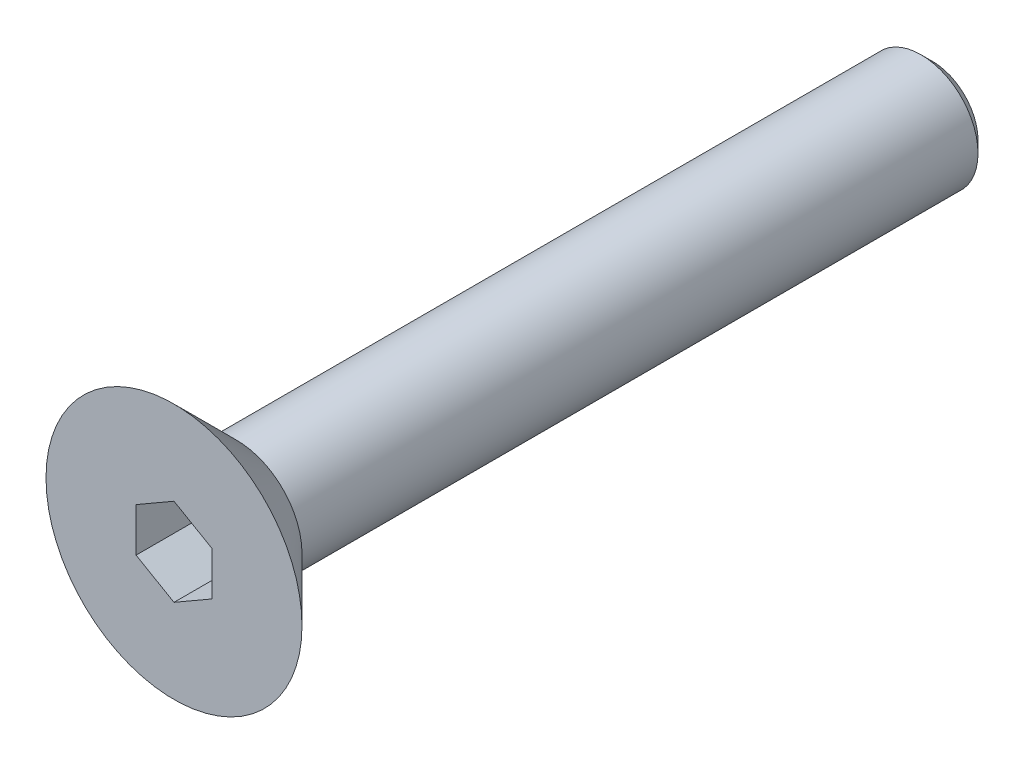
SolidWorks part; units mm, degrees
ref_plane "Front Plane" through (0, 0, 0) normal (0, 0, 1) x (1, 0, 0)
ref_plane "Top Plane" through (0, 0, 0) normal (0, 1, 0) x (1, 0, 0)
ref_plane "Right Plane" through (0, 0, 0) normal (1, 0, 0) x (0, 0, -1)
sketch "Sketch1" plane through (0, 0, 0) normal (0, 0, 1) x (1, 0, 0)
  circle A0 centre (0, 0) radius 3.375
  dimension "D1" = 6.75
extrude "Boss-Extrude1" add sketch "Sketch1" along normal blind 1.65
sketch "Sketch2" plane through (0, 0, 0) normal (0, 0, -1) x (-1, 0, 0)
  circle A0 centre (0, 0) radius 1.5
  dimension "D1" = 3
extrude "Boss-Extrude2" add sketch "Sketch2" along normal blind 18.35
chamfer "Chamfer1" distance 0.3 angle 45 1 edges at (-1.5, 0, -18.35)
sketch "Sketch3" plane through (0, 0, 1.65) normal (0, 0, 1) x (1, 0, 0)
  line L1 (0, 1.1547) -> (-1, 0.5774)
  line L2 (-1, 0.5774) -> (-1, -0.5774)
  line L3 (-1, -0.5774) -> (0, -1.1547)
  line L4 (0, -1.1547) -> (1, -0.5774)
  line L5 (1, -0.5774) -> (1, 0.5774)
  line L6 (1, 0.5774) -> (0, 1.1547)
  circle A0 centre (0, 0) radius 1 construction
  dimension "D1" = 2
extrude "Cut-Extrude1" cut sketch "Sketch3" against normal blind 2
chamfer "Chamfer2" distance 1.65 angle 45 1 edges at (3.375, 0, 0)
